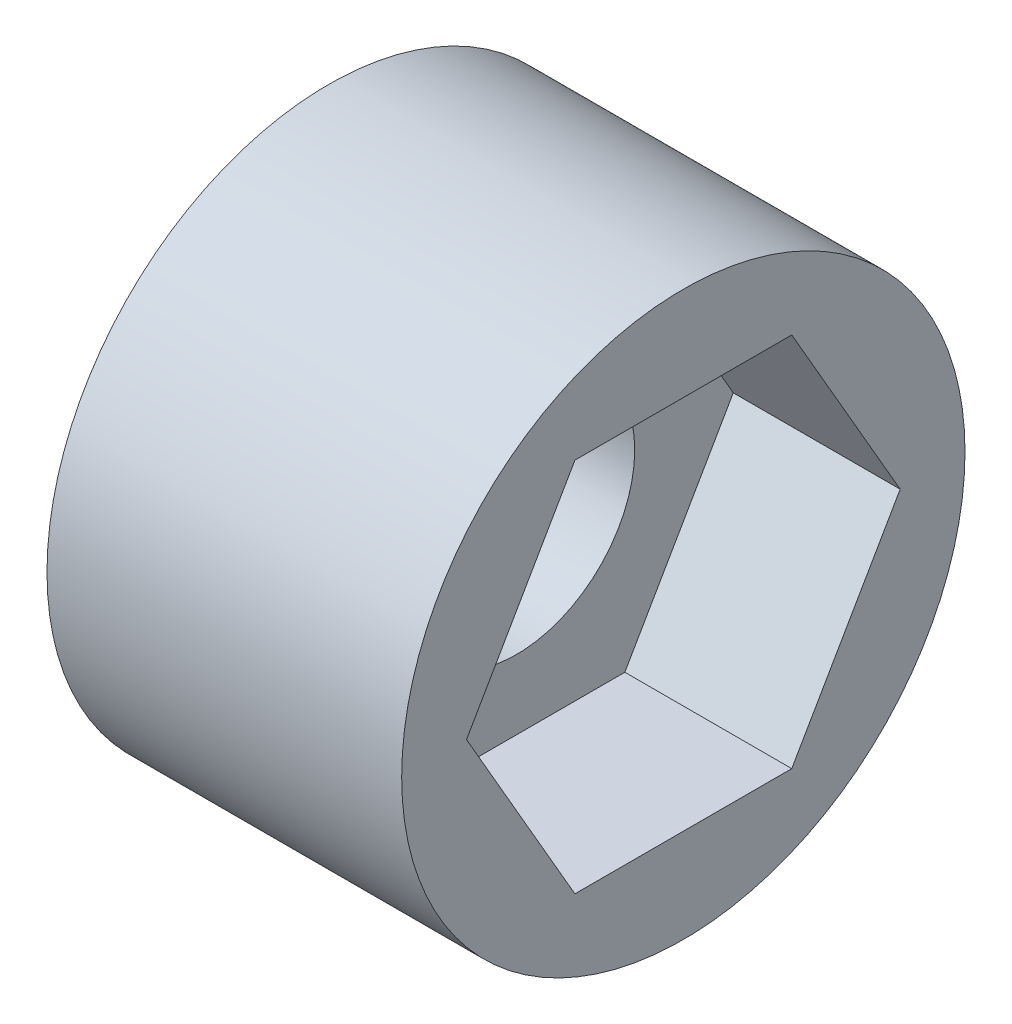
SolidWorks part; units mm, degrees
material "PET"
ref_plane "Front" through (0, 0, 0) normal (0, 0, 1) x (1, 0, 0)
ref_plane "Top" through (0, 0, 0) normal (0, 1, 0) x (1, 0, 0)
ref_plane "Right" through (0, 0, 0) normal (1, 0, 0) x (0, 0, -1)
sketch "Sketch1" plane through (0, 0, 0) normal (1, 0, 0) x (0, 0, -1)
  line L1 (7.3323, 0) -> (3.6662, 6.35)
  line L2 (3.6662, 6.35) -> (-3.6662, 6.35)
  line L3 (-3.6662, 6.35) -> (-7.3323, 0)
  line L4 (-7.3323, 0) -> (-3.6662, -6.35)
  line L5 (-3.6662, -6.35) -> (3.6662, -6.35)
  line L6 (3.6662, -6.35) -> (7.3323, 0)
  circle A0 centre (0, 0) radius 6.35 construction
  circle A1 centre (0, 0) radius 9.525
  dimension "D2" = 19.05
  dimension "D1" = 12.7
extrude "Boss-Extrude1" add sketch "Sketch1" along normal blind 11.994
sketch "Sketch2" plane through (0, 0, 0) normal (-1, 0, 0) x (0, 0, 1)
  line L1 (7.3323, 0) -> (3.6662, 6.35)
  line L2 (3.6662, 6.35) -> (-3.6662, 6.35)
  line L3 (-3.6662, 6.35) -> (-7.3323, 0)
  line L4 (-7.3323, 0) -> (-3.6662, -6.35)
  line L5 (-3.6662, -6.35) -> (3.6662, -6.35)
  line L6 (3.6662, -6.35) -> (7.3323, 0)
  circle A0 centre (0, 0) radius 6.35 construction
  circle A1 centre (0, 0) radius 4
  dimension "D2" = 8
  dimension "D1" = 12.7
extrude "Boss-Extrude2" add sketch "Sketch2" against normal blind 6.35
